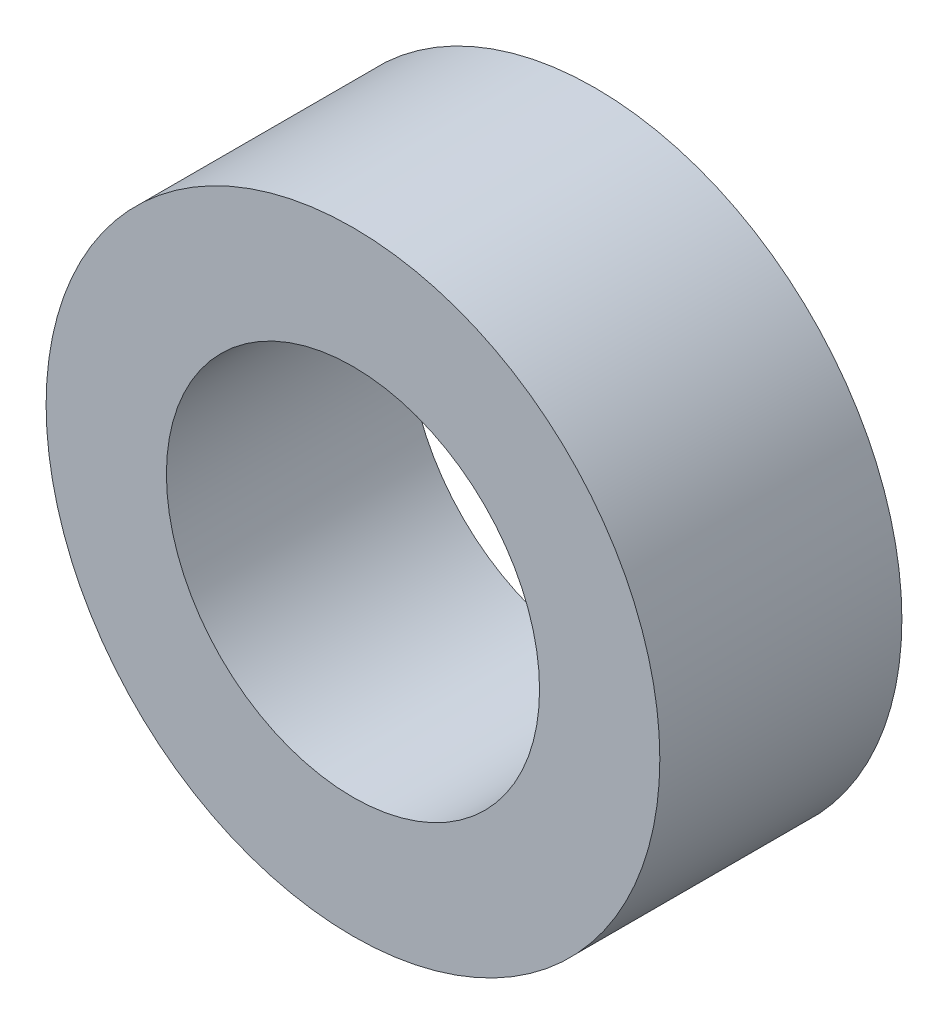
SolidWorks part; units mm, degrees
ref_plane "Front Plane" through (0, 0, 0) normal (0, 0, 1) x (1, 0, 0)
ref_plane "Top Plane" through (0, 0, 0) normal (0, 1, 0) x (1, 0, 0)
ref_plane "Right Plane" through (0, 0, 0) normal (1, 0, 0) x (0, 0, -1)
sketch "Sketch1" plane through (0, 0, 0) normal (0, 0, 1) x (1, 0, 0)
  circle A0 centre (0, 0) radius 7.9375 construction
  circle A1 centre (0, 0) radius 4.826 construction
  point P4 (0, 7.9375)
  dimension "ID" = 9.652
  dimension "OD" = 15.875
sketch "Sketch2" plane through (0, 0, 0) normal (1, 0, 0) x (0, 0, -1)
  line L0 (-152.4, 7.9375) -> (152.4, 7.9375) construction
  point P2 (132.5563, 7.9375)
  point P3 (-132.5563, 7.9375)
  dimension "Length" = 304.8
  dimension "D1" = 19.8438
  dimension "D2" = 19.8438
sketch "Sketch3" plane through (0, 0, 0) normal (0, 0, 1) x (1, 0, 0)
  circle A0 centre (0, 0) radius 4.826 construction
  circle A1 centre (0, 0) radius 7.9375 construction
  circle A2 centre (0, 0) radius 4.826
  circle A3 centre (0, 0) radius 7.9375
extrude "Boss-Extrude1" add sketch "Sketch3" against normal up to vertex (152.4 mm away) and the other way up to vertex (152.4 mm away) up to point (0, 7.9375, -152.4) other way up to point (0, 7.9375, 152.4)
sketch "Sketch4" plane through (0, 0, 152.4) normal (0, 0, 1) x (1, 0, 0)
  circle A0 centre (0, 0) radius 7.9375
extrude "Cut-Extrude1" cut sketch "Sketch4" against normal blind 298.5389
equation "\"D1@Sketch2\"=\"OD@Sketch1\"*1.25"
equation "\"D2@Sketch2\"=\"D1@Sketch2\""
